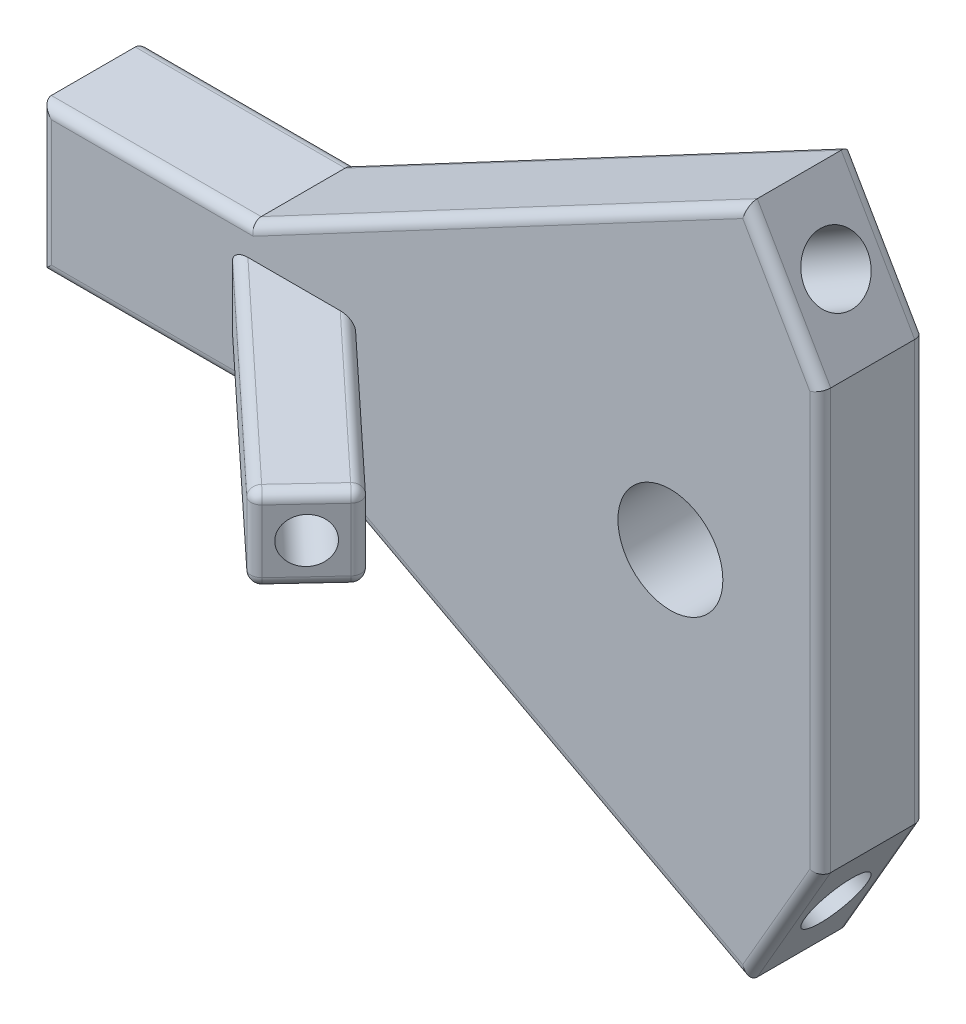
SolidWorks part; units mm, degrees
ref_plane "Plan de face" through (0, 0, 0) normal (0, 0, 1) x (1, 0, 0)
ref_plane "Plan de dessus" through (0, 0, 0) normal (0, 1, 0) x (1, 0, 0)
ref_plane "Plan de droite" through (0, 0, 0) normal (1, 0, 0) x (0, 0, -1)
sketch "Esquisse1" plane through (0, 0, 0) normal (0, 0, 1) x (1, 0, 0)
  line L0 (-20, -7) -> (-20, 7)
  line L1 (-20, 7) -> (0, 7)
  line L2 (0, 7) -> (47.282, 32.1244)
  line L3 (54.282, 20) -> (54.282, -20)
  line L4 (47.282, 32.1244) -> (54.282, 20)
  line L5 (-64.04, 0) -> (20.5013, 0) construction
  line L6 (47.282, -32.1244) -> (54.282, -20)
  line L7 (47.282, 32.1244) -> (23.6391, 18.4741) construction
  line L8 (23.6391, 18.4741) -> (30.6391, 6.3497) construction
  line L9 (0, -7) -> (47.282, -32.1244)
  line L10 (-20, -7) -> (0, -7)
  line L11 (30.6391, 6.3497) -> (54.282, 20) construction
  line L12 (47.282, -32.1244) -> (32.2056, -23.42) construction
  line L13 (32.2056, -23.42) -> (39.2056, -11.2956) construction
  line L14 (39.2056, -11.2956) -> (54.282, -20) construction
  dimension "D1" = 14
  dimension "D2" = 14
  dimension "D3" = 20
  dimension "D4" = 150
  dimension "D5" = 0
  dimension "D6" = 60
  dimension "D7" = 14
  dimension "D8" = 40
extrude "Boss.-Extru.2" add sketch "Esquisse1" along normal blind 10
sketch "Esquisse6" plane through (49.3718, 28.5048, 0) normal (0.866, 0.5, 0) x (0.5, -0.866, 0)
  line L0 (2.8205, 0) -> (2.8205, -10) construction
  line L1 (9.8205, 0) -> (-4.1795, 0) construction
  line L2 (9.8205, -10) -> (-4.1795, -10) construction
  circle A0 centre (2.8205, -5) radius 3
  point P8 (2.8205, -5)
  dimension "D1" = 6
extrude "Enlèv. mat.-Extru.4" cut sketch "Esquisse6" against normal blind 20
sketch "Esquisse7" plane through (49.3718, -28.5048, 0) normal (0.866, -0.5, 0) x (-0.5, -0.866, 0)
  line L0 (-9.8205, -5) -> (4.1795, -5) construction
  line L1 (-9.8205, -10) -> (-9.8205, 0) construction
  line L2 (4.1795, -10) -> (4.1795, 0) construction
  circle A0 centre (-2.8205, -5) radius 3
  dimension "D1" = 6
extrude "Enlèv. mat.-Extru.5" cut sketch "Esquisse7" against normal blind 20
sketch "Esquisse8" plane through (0, 0, 0) normal (0, 0, -1) x (-1, 0, 0)
  line L0 (20, 7) -> (20, -7) construction
  circle A0 centre (-40, 0) radius 5
  point P4 (20, 0)
  dimension "D2" = 10
  dimension "D1" = 60
extrude "Enlèv. mat.-Extru.6" cut sketch "Esquisse8" against normal blind 20
sketch "Esquisse9" plane through (0, 0, 10) normal (0, 0, 1) x (1, 0, 0)
  line L0 (0, 7) -> (0, -7) construction
  line L1 (0, -7) -> (10, -7) construction
  line L2 (10, -7) -> (10, 7) construction
  line L3 (10, 7) -> (0, 7) construction
  dimension "D1" = 10
sketch3d "Esquisse3D2"
  line L0 (10, -7, 10) -> (10, 7, 10) construction
  line L1 (-11.9406, 4, -10.46) -> (24.6271, 4, 23.64)
  line L2 (-11.9406, -4, -10.46) -> (-11.9406, 4, -10.46)
  line L3 (-11.9406, -4, -10.46) -> (24.6271, -4, 23.64)
  line L4 (24.6271, 4, 23.64) -> (24.6271, -4, 23.64)
  line L5 (9.9951, -4, 9.9954) -> (9.9951, 4, 9.9954) construction
  point P7 (-0.3366, 0, 0.361)
  dimension "D1" = 43
  dimension "D2" = 4
  dimension "D3" = 8
  dimension "D4" = 20
  dimension "D5" = 50
  dimension "D6" = 50
extrude "Boss.-Extru.3" add sketch "Esquisse3D2" along direction (0, 0, 1) on the side of the normal blind 10.94
sketch "Esquisse11" plane through (0, -4, 0) normal (0, -1, 0) x (-1, 0, 0)
  line L0 (-24.6271, -23.64) -> (-19.1704, -29.4915)
  line L1 (-24.6271, -34.58) -> (1.7317, -10) construction
  line L2 (-21.0886, -31.2803) -> (-24.6271, -34.58)
  line L3 (-24.6271, -34.58) -> (-24.6271, -23.64)
  line L4 (-19.1704, -29.4915) -> (-24.6271, -34.58)
  line M6 (-24.6271, -23.64) -> (-24.6271, -34.58)
  line M7 (-24.6271, -34.58) -> (1.7317, -10)
extrude "Enlèv. mat.-Extru.9" cut sketch "Esquisse11" against normal blind 10 contours L0 M6 M7 region at (22.8082, -4, 29.2372)
sketch "Esquisse14" plane through (0, -4, 0) normal (0, -1, 0) x (-1, 0, 0)
  line L1 (11.9406, 0) -> (-9.1147, 0)
  line L2 (11.9406, 0) -> (11.9406, 15.6279)
  line L3 (11.9406, 15.6279) -> (-9.1147, 15.6279)
  line L4 (-9.1147, 0) -> (-9.1147, 15.6279)
extrude "Enlèv. mat.-Extru.10" cut sketch "Esquisse14" against normal blind 10
sketch "Esquisse15" plane through (24.9637, 0, 23.279) normal (0.7314, 0, 0.682) x (0.682, 0, -0.7314)
  line L0 (-4.4941, 4) -> (-4.4941, -4) construction
  line L1 (-0.4936, 4) -> (-8.4946, 4) construction
  line L2 (-0.4936, -4) -> (-8.4946, -4) construction
  line L3 (-0.4936, 0) -> (-8.4946, 0) construction
  line L4 (-0.4936, 4) -> (-0.4936, -4) construction
  line L5 (-8.4946, 4) -> (-8.4946, -4) construction
  circle A0 centre (-4.4941, 0) radius 2.15
  point P9 (-4.4941, 0)
  dimension "D1" = 4.3
extrude "Enlèv. mat.-Extru.11" cut sketch "Esquisse15" against normal blind 20
sketch "Esquisse18" plane through (0, 0, 0) normal (0, 0, -1) x (-1, 0, 0)
  line L0 (0, 7) -> (0, -7) construction
  line L1 (0, -7) -> (-10, -7) construction
  line L2 (-10, -7) -> (-10, 7) construction
  line L3 (-10, 7) -> (0, 7) construction
  dimension "D1" = 10
sketch3d "Esquisse3D3" plane through (0, 0, 0) normal (0, 0, 1) x (1, 0, 0)
  dimension "D1" = 41.8
sketch "Esquisse19" plane through (4.4427, 0, 4.9688) normal (-0.6665, 0, -0.7455) x (-0.7455, 0, 0.6665)
  line L0 (-7.4548, -7) -> (-7.4548, 7) construction
  line L1 (17.5452, 4) -> (-27.4548, 4)
  line L2 (17.5452, 4) -> (17.5452, -4)
  line L3 (17.5452, -4) -> (-27.4548, -4)
  line L4 (-27.4548, 4) -> (-27.4548, -4)
  line L5 (-7.4548, -7) -> (-7.4548, 7)
  dimension "D1" = 8
  dimension "D2" = 25
  dimension "D3" = 45
  dimension "D4" = 3
extrude "Boss.-Extru.6" add sketch "Esquisse19" along normal blind 8 contours L3 L4 L1 L2
sketch "Esquisse20" plane through (0, -4, 0) normal (0, -1, 0) x (-1, 0, 0)
  line L0 (8.6369, -16.6633) -> (13.9692, -10.6995)
  line L1 (13.9692, -10.6995) -> (13.1868, -10)
  line L2 (8.6369, -16.6633) -> (1.4638, -10.2498)
  line L3 (1.4638, -10.2498) -> (1.7136, -10)
  line L4 (-10, -10) -> (13.1868, -10) construction
  line L5 (1.7136, -10) -> (13.1868, -10)
extrude "Enlèv. mat.-Extru.13" cut sketch "Esquisse20" against normal blind 8
sketch "Esquisse21" plane through (20.4669, 0, -18.2995) normal (0.7455, 0, -0.6665) x (-0.6665, 0, -0.7455)
  line L0 (1.3347, 0) -> (-6.6653, 0) construction
  line L1 (1.3347, 4) -> (1.3347, -4) construction
  line L2 (-6.6653, 4) -> (-6.6653, -4) construction
  line L3 (-2.6653, 4) -> (-2.6653, -4) construction
  line L4 (1.3347, 4) -> (-6.6653, 4) construction
  line L5 (1.3347, -4) -> (-6.6653, -4) construction
  circle A0 centre (-2.6653, 0) radius 2.15
  point P15 (-2.6653, 0)
  dimension "D1" = 4.3
extrude "Enlèv. mat.-Extru.14" cut sketch "Esquisse21" against normal blind 20
sketch "Esquisse4" plane through (-20, 0, 0) normal (-1, 0, 0) x (0, 0, 1)
  line L0 (0, 0) -> (10, 0) construction
  line L1 (0, 7) -> (0, -7) construction
  line L2 (10, 7) -> (10, -7) construction
  circle A0 centre (5, 0) radius 3
  dimension "D1" = 6
extrude "Enlèv. mat.-Extru.3" cut sketch "Esquisse4" against normal blind 20
fillet "Congé1" radius 1 16 edges at (24.9095, 0, -13.3306) (22.2434, 4, -16.3126) (19.5773, 0, -19.2945) (22.2434, -4, -16.3126) (19.1704, 0, 29.4915) (17.4548, -4, -6.6653) (17.4548, 4, -6.6653) (8.7874, 4, -9.6472) (8.7874, -4, -9.6472)
fillet "Congé2" radius 1 16 edges at (-10, -7, 0) (-10, -7, 10) (-20, 0, 0) (-10, 7, 0) (-20, 0, 10) (-10, 7, 10) (23.641, 19.5622, 0) (23.641, 19.5622, 10) (50.782, 26.0622, 0) (50.782, 26.0622, 10) (23.641, -19.5622, 10) (23.641, -19.5622, 0) (50.782, -26.0622, 0) (50.782, -26.0622, 10) (54.282, 0, 0) (54.282, 0, 10)
